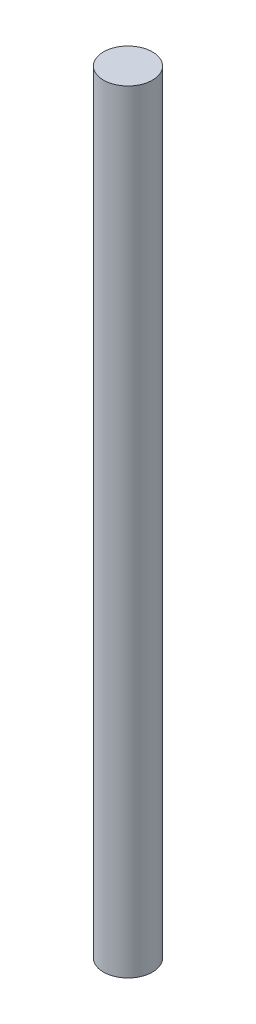
SolidWorks part; units mm, degrees
ref_plane "Front Plane" through (0, 0, 0) normal (0, 0, 1) x (1, 0, 0)
ref_plane "Top Plane" through (0, 0, 0) normal (0, 1, 0) x (1, 0, 0)
ref_plane "Right Plane" through (0, 0, 0) normal (1, 0, 0) x (0, 0, -1)
sketch "Sketch1" plane through (0, 0, 0) normal (0, 1, 0) x (1, 0, 0)
  circle A0 centre (0, 0) radius 3.17
extrude "Boss-Extrude1" add sketch "Sketch1" along normal blind 100
